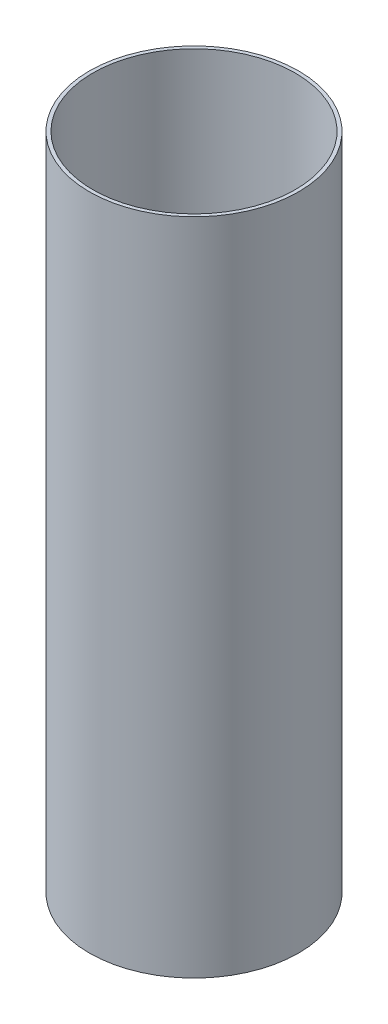
SolidWorks part; units mm, degrees
material "PC High Viscosity"
ref_plane "Front Plane" through (0, 0, 0) normal (0, 0, 1) x (1, 0, 0)
ref_plane "Top Plane" through (0, 0, 0) normal (0, 1, 0) x (1, 0, 0)
ref_plane "Right Plane" through (0, 0, 0) normal (1, 0, 0) x (0, 0, -1)
sketch "Sketch1" plane through (0, 0, 0) normal (0, 0, 1) x (1, 0, 0)
  line L0 (0, 0) -> (0, 600) construction
  line L1 (95.25, 0) -> (92.075, 0)
  line L2 (95.25, 600) -> (95.25, 0)
  line L3 (92.075, 0) -> (92.075, 600)
  line L4 (92.075, 600) -> (95.25, 600)
  line L5 (0, 600) -> (92.075, 600) construction
  line L6 (0, 0) -> (92.075, 0) construction
  dimension "D1" = 92.075
  dimension "D2" = 3.175
  dimension "D3" = 600
revolve "Revolve1" add sketch "Sketch1" angle 360 about L0
ref_plane "Plane1" through (0, 0, 101) normal (0, 0, 1) x (1, 0, 0)
ref_plane "Plane2" through (95.25, 0, 0) normal (1, 0, 0) x (0, 0, -1)
sketch "Sketch3" plane through (95.25, 0, 0) normal (1, 0, 0) x (0, 0, -1)
  line L0 (92.075, 600) -> (-92.075, 600) construction
  circle A0 centre (0, 580.95) radius 3.175
  dimension "D1" = 19.05
  dimension "D2" = 6.35
extrude "Cut-Extrude1" [suppressed] cut sketch "Sketch3" against normal up to surface (3.2298 mm away) up to face at (0, 0, -92.075)
pattern_circular "CirPattern1" [suppressed] count 2 every 180 of bodies 106
